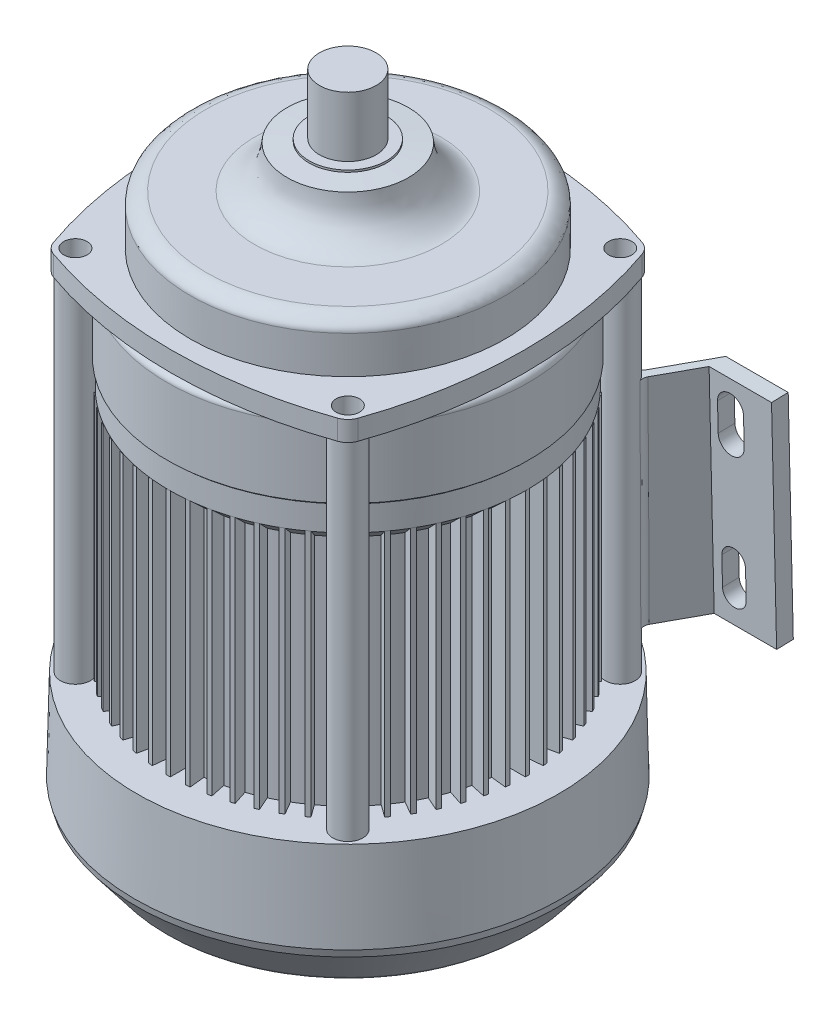
SolidWorks part; units mm, degrees
ref_plane "Front Plane" through (0, 0, 0) normal (0, 0, 1) x (1, 0, 0)
ref_plane "Top Plane" through (0, 0, 0) normal (0, 1, 0) x (1, 0, 0)
ref_plane "Right Plane" through (0, 0, 0) normal (1, 0, 0) x (0, 0, -1)
sketch "Sketch1" plane through (0, 0, 0) normal (0, 0, 1) x (1, 0, 0)
  line L0 (-69.3462, -139.209) -> (170.5518, -139.209) construction
sketch "Sketch3" plane through (0, 0, 0) normal (0, 0, 1) x (1, 0, 0)
  line L0 (-8.5, 0) -> (0, 0) construction
  line L1 (0, 8) -> (0, -197)
  line L2 (-8.5, 0) -> (-8.5, 8)
  line L3 (-8.5, 0) -> (-8.5, -10)
  line L4 (-8.5, -10) -> (-11.6, -10)
  line L5 (-11.6, -10) -> (-11.6, -10.6039)
  line L6 (-27.95, -23.6039) -> (-42.45, -23.6039)
  line L7 (-42.45, -23.6039) -> (-42.45, -27.2539) construction
  line L8 (-42.45, -27.2539) -> (-47.2, -27.2539) construction
  line L9 (-47.2, -27.2539) -> (-47.2, -44.5)
  line L10 (-45.45, -24.7539) -> (-45.45, -27.2539) construction
  line L11 (-11.6, -10.6039) -> (-18.2, -11.0655)
  line L12 (-22.2177, -20.8703) -> (-19.1856, -16.9994) construction
  line L13 (-20.1532, -29.2223) -> (-16.2468, 7.0914) construction
  line L16 (-52.9, -44.5) -> (-47.2, -44.5)
  line L17 (-8.5, 8) -> (0, 8)
  line L18 (0, 8) -> (0, 15.3127) construction
  line L19 (0, -197) -> (-2, -197)
  line L20 (-54.1917, -66.45) -> (-54.1917, -67.05) construction
  line L21 (-54.1917, -46.3) -> (-54.1917, -66.45)
  line L22 (-54.1917, -66.45) -> (-53.5483, -67.05)
  line L23 (-53.5483, -67.05) -> (-53.5483, -74.55)
  line L24 (-47.2, -44.5) -> (0, -44.5)
  line L25 (-52.9, -44.5) -> (0, -44.5) construction
  line L26 (-53.5483, -74.55) -> (-49.2588, -78.55)
  line L27 (-49.2588, -78.55) -> (-49.2588, -148.55)
  line L28 (-49.2588, -148.55) -> (-63.2588, -148.55)
  line L29 (-63.2588, -148.55) -> (-63.8951, -175.55)
  line L30 (-63.8951, -175.55) -> (-63.2588, -177.8444)
  line L31 (-63.2588, -177.8444) -> (-54.4331, -189.3444)
  line L33 (-63.2588, -148.55) -> (-63.2588, -175.55) construction
  arc A1 (-52.9, -44.5) -> (-54.1917, -46.3) centre (-52.2917, -46.3) ccw
  spline S0 degree 3 poles (-18.2, -11.0655) (-18.4832, -13.6984) (-18.7961, -16.5493) (-22.6179, -21.3727) (-26.2709, -23.6039) (-27.95, -23.6039) knots 0 0 0 0 0.435029 0.535029 1 1 1 1
  spline S2 degree 3 poles (-47.2, -27.2539) (-47.2, -26.1869) (-45.306, -24.4455) (-43.5167, -23.6039) (-42.45, -23.6039) knots 0 0 0 0 0.468038 1 1 1 1
  spline S3 degree 3 poles (-54.4331, -189.3444) (-51.4904, -193.1787) (-12.5784, -196.5978) (-6.2, -197) (-2, -197) knots 0 0 0 0 0.440369 1 1 1 1
  dimension "D13" = 6.6
  dimension "D14" = 52.5
  dimension "D21" = 1.9
  dimension "D23" = 1.8
  dimension "D37" = 14.5
  dimension "D38" = 5.5971
  dimension "D18" = 3.2012
  dimension "D19" = 3.2
  dimension "D22" = 12.6
  dimension "D39" = 8.827
  dimension "D2" = 3.65
  dimension "D3" = 4.75
  dimension "D4" = 2.5
  dimension "D5" = 3
  dimension "D6" = 10
  dimension "D7" = 3.1
  dimension "D8" = 0.6039
  dimension "D9" = 14.5
  dimension "D10" = 13
  dimension "D11" = 16.35
  dimension "D12" = 94
  dimension "D15" = 5.7
  dimension "D16" = 2
  dimension "D17" = 8
  dimension "D20" = 8.5
  dimension "D24" = 20.15
  dimension "D25" = 47
  dimension "D26" = 0.6
  dimension "D27" = 7.5
  dimension "D28" = 4
  dimension "D29" = 70
  dimension "D30" = 14
  dimension "D31" = 197
  dimension "D32" = 1.35
  dimension "D33" = 27
  dimension "D34" = 15.5
  dimension "D35" = 142.495
  dimension "D36" = 11.5
  dimension "D40" = 6.14
revolve "Revolve4" add sketch "Sketch3" angle 360 about L18 region at (-18.8402, -27.2585, 0) region at (-27.0884, -121.9509, 0)
sketch "Sketch5" plane through (0, -148.55, 0) normal (0, 1, 0) x (1, 0, 0)
  line L0 (0, 0) -> (0, -63.2588) construction
  line L1 (-0.625, -53.8549) -> (0.625, -53.8549)
  line L6 (-0.625, -53.8549) -> (-0.625, -49.2549)
  line L7 (0.625, -53.8549) -> (0.625, -49.2549)
  circle A0 centre (0, 0) radius 63.2588 construction
  circle A1 centre (0, 0) radius 49.2588 construction
  circle A2 centre (0, 0) radius 49.2588 construction
  arc A3 (-0.625, -49.2549) -> (0.625, -49.2549) centre (0, 0) ccw
  point P0 (0, 0)
  point P10 (0, -53.8549)
  dimension "D1" = 4.6
  dimension "D2" = 1.25
extrude "Boss-Extrude2" add sketch "Sketch5" along normal up to surface (74.2893 mm away) up to face at (0, -78.55, -49.2588)
pattern_circular "CirPattern1" count 60 over 360 about axis through (0, 8, 0) along (0, -1, 0) of "Boss-Extrude2"
ref_plane "Plane1" through (0, -38.5, 0) normal (0, 1, 0) x (1, 0, 0)
sketch "Sketch6" plane through (0, -38.5, 0) normal (0, 1, 0) x (1, 0, 0)
  line L0 (0, 0) -> (57.7588, 0) construction
  line L1 (0, 0) -> (40.8417, 40.8417) construction
  line L3 (-44.8417, -44.8417) -> (44.8417, -44.8417) construction
  line L4 (-44.8417, -44.8417) -> (-44.8417, 44.8417) construction
  line L5 (-44.8417, 44.8417) -> (44.8417, 44.8417) construction
  line L6 (44.8417, -44.8417) -> (44.8417, 44.8417) construction
  line L7 (-44.8417, -44.8417) -> (44.8417, 44.8417) construction
  line L8 (-44.8417, 44.8417) -> (44.8417, -44.8417) construction
  circle A0 centre (0, 0) radius 52.9 construction
  circle A1 centre (0, 0) radius 52.9 construction
  circle A2 centre (0, 0) radius 63.2588 construction
  circle A3 centre (0, 0) radius 63.2588 construction
  circle A4 centre (0, 0) radius 57.7588 construction
  circle A14 centre (-40.8417, 40.8417) radius 4.5
  circle A18 centre (40.8417, 40.8417) radius 3.5
  circle A19 centre (40.8417, -40.8417) radius 3.5
  circle A20 centre (-40.8417, -40.8417) radius 3.5
  circle A21 centre (-40.8417, 40.8417) radius 3.5
  arc A22 (44.8417, 44.8417) -> (44.8417, -44.8417) centre (-75.8927, 0) cw
  arc A23 (-44.8417, 44.8417) -> (44.8417, 44.8417) centre (0, -75.8927) cw
  arc A24 (-44.8417, 44.8417) -> (-44.8417, -44.8417) centre (75.8927, 0) ccw
  arc A25 (-44.8417, -44.8417) -> (44.8417, -44.8417) centre (0, 75.8927) ccw
  circle A26 centre (40.8417, 40.8417) radius 4.5
  circle A27 centre (40.8417, -40.8417) radius 4.5
  circle A28 centre (-40.8417, -40.8417) radius 4.5
  point P6 (0, 0)
  point P12 (52.9, 0)
  point P20 (0, 0)
  point P27 (0, -52.9)
  dimension "D3" = 7
  dimension "D1" = 5.5
  dimension "D2" = 45
  dimension "D5" = 4
  dimension "D6" = 4
  dimension "D7" = 1
  dimension "D8" = 1
  dimension "D4" = 4
extrude "Boss-Extrude5" add sketch "Sketch6" against normal up to surface (6 mm away) contours A24 A25 A22 A23 A28 A27 A26 A14 | A28 A20 | A27 A19 | A26 A18 | A14 A21 region at (-45.2144, -38.5, -40.8417) region at (0, -38.5, 0) region at (36.4689, -38.5, -40.8417) region at (36.4689, -38.5, 40.8417) region at (-45.2144, -38.5, 40.8417) up to face at (0, -44.5, -47.2)
extrude "Boss-Extrude6" add sketch "Sketch6<4>" against normal up to surface (110.05 mm away) contours A26 A18 | A14 A21 | A27 A19 | A28 A20 region at (-45.2144, -38.5, -40.8417) region at (36.4689, -38.5, -40.8417) region at (36.4689, -38.5, 40.8417) region at (-45.2144, -38.5, 40.8417) up to face at (0, -148.55, -63.2588)
sketch "Sketch6<4>" plane through (0, -38.5, 0) normal (0, 1, 0) x (1, 0, 0) same geometry as "Sketch6"
fillet "Fillet2" radius 5 4 edges at (44.8417, -41.5, 44.8417) (44.8417, -41.5, -44.8417) (-44.8417, -41.5, 44.8417) (-44.8417, -41.5, -44.8417)
ref_plane "Plane2" through (0, 1.4075, -59.7249) normal (0, 0.0236, -0.9997) x (-1, 0, 0)
sketch "Sketch7" plane through (0, 1.4075, -59.7249) normal (0, 0.0236, -0.9997) x (-1, 0, 0)
  line L0 (-58, -137.7) -> (-70.6, -137.7)
  line L1 (-70.6, -137.7) -> (-70.6, -72.8)
  line L2 (-70.6, -72.8) -> (-53.75, -72.8)
  line L3 (0, 0) -> (0, -214.7784) construction
  line L4 (-58.1192, -133.2) -> (-58.1192, -117.2) construction
  line L5 (-58.1192, -120.925) -> (-58.1192, -129.475) construction
  line L6 (-54.5692, -120.925) -> (-54.5692, -129.475)
  line L7 (-61.6692, -120.925) -> (-61.6692, -129.475)
  line L8 (-58.1192, -76.9) -> (-58.1192, -92.9) construction
  line L9 (-58.1192, -89.175) -> (-58.1192, -80.625) construction
  line L10 (-62.0192, -89.175) -> (-62.0192, -80.625)
  line L11 (-54.2192, -89.175) -> (-54.2192, -80.625)
  line L12 (-51.8792, -72.8) -> (-51.8792, -137.7)
  line L13 (-53.75, -72.8) -> (-51.8792, -72.8)
  line L14 (-58, -137.7) -> (-51.8792, -137.7)
  arc A0 (-54.5692, -120.925) -> (-61.6692, -120.925) centre (-58.1192, -120.925) ccw
  arc A1 (-61.6692, -129.475) -> (-54.5692, -129.475) centre (-58.1192, -129.475) ccw
  arc A2 (-62.0192, -89.175) -> (-54.2192, -89.175) centre (-58.1192, -89.175) ccw
  arc A3 (-54.2192, -80.625) -> (-62.0192, -80.625) centre (-58.1192, -80.625) ccw
  point P10 (-58.1192, -125.2)
  point P19 (-58.1192, -84.9)
  dimension "D10" = 3.55
  dimension "D13" = 3.9
  dimension "D1" = 58
  dimension "D2" = 137.7
  dimension "D3" = 12.6
  dimension "D4" = 72.8
  dimension "D5" = 53.75
  dimension "D6" = 16
  dimension "D7" = 4.5
  dimension "D8" = 58.1192
  dimension "D9" = 8.55
  dimension "D11" = 76.9
  dimension "D12" = 8.55
  dimension "D14" = 6.24
extrude "Boss-Extrude7" add sketch "Sketch7" against normal blind 5 separate body
sketch "Sketch9" plane through (0, -137.6618, -3.2442) normal (0, -0.9997, -0.0236) x (1, 0, 0)
  line L0 (51.8792, -54.7415) -> (43.2173, -39.9001)
  line L1 (51.8792, -59.7415) -> (40.8417, -40.8295)
  line L2 (51.8792, -59.7415) -> (51.8792, -54.7415)
  line L3 (40.8417, -40.8295) -> (43.2173, -39.9001)
  ellipse E0 centre (40.8417, -37.3305) end of major axis (44.3417, -37.3305) minor radius 3.499 construction
  ellipse E1 centre (40.8417, -37.3305) end of major axis (44.3417, -37.3305) minor radius 3.499 construction
  point P13 (40.8417, -37.3305)
extrude "Boss-Extrude8" add sketch "Sketch9" against normal up to surface (64.9 mm away) up to face at (61.2396, -71.4312, -58.9407)
mirror "Mirror2" about plane through (0, 0, 0) normal (1, 0, 0) of "Boss-Extrude8", "Boss-Extrude7"
extrude "Cut-Extrude1" cut sketch "Sketch6<5>" against normal up to surface (110.05 mm away) contours A18 | A21 region at (40.8417, -38.5, -40.8417) region at (-40.8417, -38.5, -40.8417) up to face at (-40.8417, -148.55, 36.3417)
sketch "Sketch6<5>" plane through (0, -38.5, 0) normal (0, 1, 0) x (1, 0, 0) same geometry as "Sketch6"
fillet "Fillet3" radius 2.5 4 edges at (-41.9484, -104.6306, -45.2034) (-44.1271, -103.8104, -43.9167) (41.9484, -104.6306, -45.2034) (44.1271, -103.8104, -43.9167)
